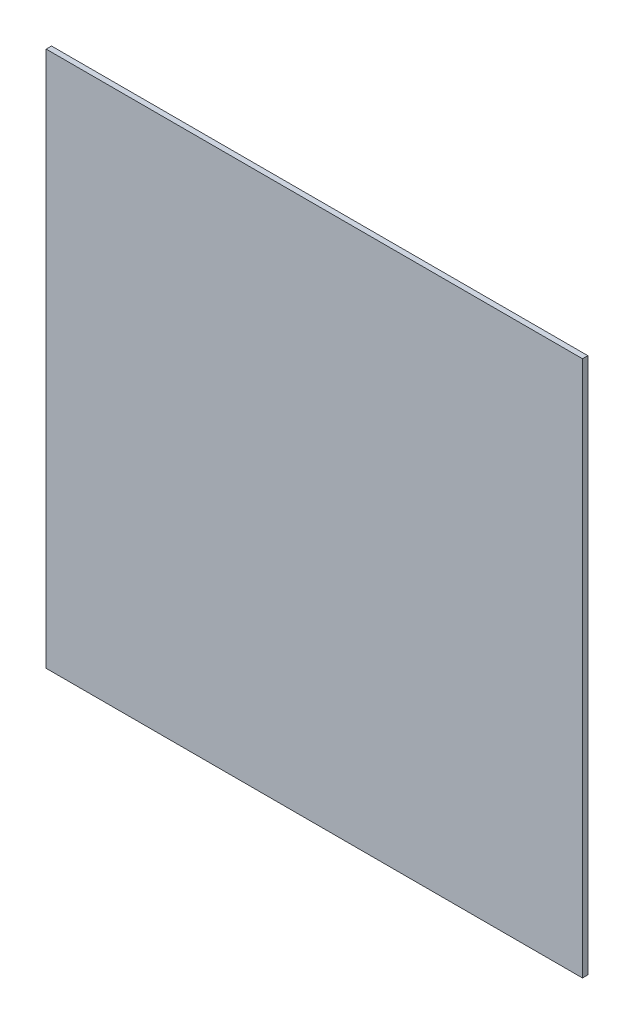
SolidWorks part; units mm, degrees
ref_plane "Front Plane" through (0, 0, 0) normal (0, 0, 1) x (1, 0, 0)
ref_plane "Top Plane" through (0, 0, 0) normal (0, 1, 0) x (1, 0, 0)
ref_plane "Right Plane" through (0, 0, 0) normal (1, 0, 0) x (0, 0, -1)
other "Configuration Table"
sketch "Sketch1" plane through (0, 0, 0) normal (0, 0, 1) x (1, 0, 0)
  line L1 (0, 0) -> (1000, 0)
  line L2 (0, 0) -> (0, 1000)
  line L3 (0, 1000) -> (1000, 1000)
  line L4 (1000, 0) -> (1000, 1000)
sheet metal parameters "Sheet-Metal1" thickness 10 parameters "D1"=0.7366
base flange "Base-Flange1" sketch "Sketch1" thickness 10 reverse thickness direction yes parameters "D1"=0.7366
flat pattern "Flat-Pattern1" [suppressed]
sketch "Bend-Lines1" plane through (0, 0, 0) normal (0, 1, 0) x (-1, 0, 0)
